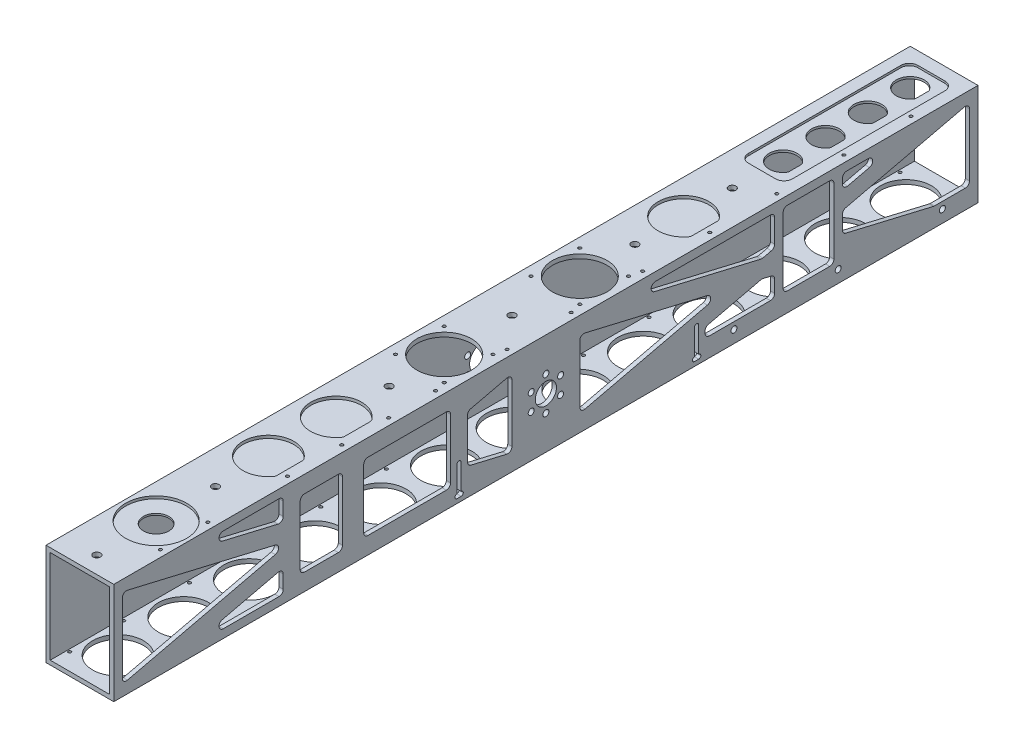
SolidWorks part; units mm, degrees
material "6061-T6 (SS)"
ref_plane "Front Plane" through (0, 0, 0) normal (0, 0, 1) x (1, 0, 0)
ref_plane "Top Plane" through (0, 0, 0) normal (0, 1, 0) x (1, 0, 0)
ref_plane "Right Plane" through (0, 0, 0) normal (1, 0, 0) x (0, 0, -1)
sketch "Sketch1" plane through (0, 0, 0) normal (0, 0, 1) x (1, 0, 0)
  line L0 (3.175, 3.175) -> (3.175, 73.025)
  line L1 (0, 0) -> (50.8, 0)
  line L2 (0, 0) -> (0, 76.2)
  line L3 (0, 76.2) -> (50.8, 76.2)
  line L4 (50.8, 0) -> (50.8, 76.2)
  line L5 (3.175, 73.025) -> (47.625, 73.025)
  line L6 (47.625, 3.175) -> (47.625, 73.025)
  line L7 (3.175, 3.175) -> (47.625, 3.175)
  dimension "D1" = 76.2
  dimension "D2" = 50.8
  dimension "D3" = 3.175
extrude "Boss-Extrude1" add sketch "Sketch1" along normal blind 647.7
sketch "Sketch2" plane through (50.8, 0, 0) normal (1, 0, 0) x (0, 0, -1)
  line L0 (-323.85, 76.2) -> (-323.85, 0) construction
  line L1 (-647.7, 76.2) -> (0, 76.2) construction
  line L2 (-647.7, 0) -> (0, 0) construction
  line L3 (-121.0655, 35.0094) -> (-10.2522, 8.9357)
  line L4 (-322.3956, 82.3812) -> (1.4544, 6.1812) construction
  line L5 (-649.1544, 6.1812) -> (-325.3044, 82.3812) construction
  line L6 (-646.2456, 82.3812) -> (-322.3956, 6.1812) construction
  line L7 (-649.1544, 70.0188) -> (-325.3044, -6.1812) construction
  line L8 (-647.7, 76.2) -> (-323.85, 0) construction
  line L9 (-647.7, 0) -> (-323.85, 76.2) construction
  line L10 (-323.85, 76.2) -> (0, 0) construction
  line L11 (-323.85, 0) -> (0, 76.2) construction
  line L12 (-6.35, 6.35) -> (-6.35, 69.85)
  line L13 (-6.35, 69.85) -> (-641.35, 69.85)
  line L14 (-641.35, 69.85) -> (-641.35, 6.35)
  line L15 (-641.35, 6.35) -> (-6.35, 6.35)
  line L16 (-6.35, 12.0263) -> (-6.35, 64.1737)
  line L17 (-646.2456, -6.1812) -> (-322.3956, 70.0188) construction
  line L18 (-641.35, 64.1737) -> (-641.35, 12.0263)
  line L19 (-641.35, 6.35) -> (-620.7125, 6.35)
  line L20 (-322.3956, -6.1812) -> (1.4544, 70.0188) construction
  line L21 (-325.3044, 6.1812) -> (-1.4544, 82.3812) construction
  line L22 (-161.1978, 44.7945) -> (-81.3408, 63.5844)
  line L23 (-161.1978, 31.4055) -> (-81.3408, 12.6156)
  line L24 (-241.782, 69.85) -> (-82.068, 69.85)
  line L25 (-647.7, 69.85) -> (0, 69.85)
  line L26 (-641.35, 69.85) -> (-620.7125, 69.85)
  line L27 (-241.782, 6.35) -> (-82.068, 6.35)
  line L28 (-566.3592, 63.5844) -> (-486.5022, 44.7945)
  line L29 (-637.4478, 67.2643) -> (-526.6345, 41.1906)
  line L30 (-637.4478, 8.9357) -> (-526.6345, 35.0094)
  line L31 (-566.3592, 12.6156) -> (-486.5022, 31.4055)
  line L32 (-242.5092, 63.5844) -> (-162.6522, 44.7945)
  line L33 (-325.3044, 70.0188) -> (-323.85, 69.6766)
  line L34 (-294.5478, 13.418) -> (-202.7845, 35.0094)
  line L35 (-242.5092, 12.6156) -> (-162.6522, 31.4055)
  line L36 (-349.25, 59.6914) -> (-349.25, 16.5086)
  line L37 (-298.45, 59.6914) -> (-298.45, 16.5086)
  line L38 (-294.5478, 62.782) -> (-202.7845, 41.1906)
  line L39 (-121.0655, 41.1906) -> (-10.2522, 67.2643)
  line L40 (-325.3044, 70.0188) -> (-1.4544, -6.1812) construction
  line L41 (-485.0478, 44.7945) -> (-405.1908, 63.5844)
  line L42 (-444.9155, 35.0094) -> (-353.1522, 13.418)
  line L43 (-444.9155, 41.1906) -> (-353.1522, 62.782)
  line L44 (-485.0478, 31.4055) -> (-405.1908, 12.6156)
  line L45 (-565.632, 69.85) -> (-405.918, 69.85)
  line L46 (-565.632, 6.35) -> (-405.918, 6.35)
  line L47 (-26.9875, 6.35) -> (-6.35, 6.35)
  line L48 (-26.9875, 69.85) -> (-6.35, 69.85)
  arc A0 (-405.918, 6.35) -> (-405.1908, 12.6156) centre (-405.918, 9.525) ccw
  arc A1 (-565.632, 6.35) -> (-566.3592, 12.6156) centre (-565.632, 9.525) cw
  arc A2 (-641.35, 64.1737) -> (-637.4478, 67.2643) centre (-638.175, 64.1737) cw
  arc A3 (-637.4478, 8.9357) -> (-641.35, 12.0263) centre (-638.175, 12.0263) cw
  arc A4 (-82.068, 6.35) -> (-81.3408, 12.6156) centre (-82.068, 9.525) ccw
  arc A5 (-241.782, 6.35) -> (-242.5092, 12.6156) centre (-241.782, 9.525) cw
  arc A6 (-6.35, 12.0263) -> (-10.2522, 8.9357) centre (-9.525, 12.0263) cw
  arc A7 (-6.35, 64.1737) -> (-10.2522, 67.2643) centre (-9.525, 64.1737) ccw
  arc A8 (-81.3408, 63.5844) -> (-82.068, 69.85) centre (-82.068, 66.675) ccw
  arc A9 (-242.5092, 63.5844) -> (-241.782, 69.85) centre (-241.782, 66.675) cw
  arc A10 (-121.0655, 41.1906) -> (-121.0655, 35.0094) centre (-120.3383, 38.1) ccw
  arc A11 (-161.1978, 31.4055) -> (-162.6522, 31.4055) centre (-161.925, 28.3149) ccw
  arc A12 (-161.1978, 44.7945) -> (-162.6522, 44.7945) centre (-161.925, 47.8851) cw
  arc A13 (-202.7845, 35.0094) -> (-202.7845, 41.1906) centre (-203.5117, 38.1) ccw
  arc A14 (-294.5478, 13.418) -> (-298.45, 16.5086) centre (-295.275, 16.5086) cw
  arc A15 (-294.5478, 62.782) -> (-298.45, 59.6914) centre (-295.275, 59.6914) ccw
  arc A16 (-353.1522, 62.782) -> (-349.25, 59.6914) centre (-352.425, 59.6914) cw
  arc A17 (-349.25, 16.5086) -> (-353.1522, 13.418) centre (-352.425, 16.5086) cw
  arc A18 (-485.0478, 31.4055) -> (-486.5022, 31.4055) centre (-485.775, 28.3149) ccw
  arc A19 (-526.6345, 35.0094) -> (-526.6345, 41.1906) centre (-527.3617, 38.1) ccw
  arc A20 (-444.9155, 35.0094) -> (-444.9155, 41.1906) centre (-444.1883, 38.1) cw
  arc A21 (-485.0478, 44.7945) -> (-486.5022, 44.7945) centre (-485.775, 47.8851) cw
  arc A22 (-405.1908, 63.5844) -> (-405.918, 69.85) centre (-405.918, 66.675) ccw
  arc A23 (-566.3592, 63.5844) -> (-565.632, 69.85) centre (-565.632, 66.675) cw
  point P69 (-592.988, 6.35)
  point P92 (-161.925, 44.6234)
  point P99 (-298.45, 63.7001)
  point P106 (-485.775, 31.5766)
  point P111 (-458.0505, 38.1)
  point P118 (-592.988, 69.85)
  dimension "D13" = 3.175
  dimension "D11" = 25.4
  dimension "D12" = 25.4
  dimension "D1" = 6.35
  dimension "D2" = 6.35
  dimension "D3" = 6.35
  dimension "D4" = 6.35
  dimension "D5" = 6.35
  dimension "D6" = 6.35
  dimension "D7" = 6.35
  dimension "D8" = 6.35
  dimension "D9" = 6.35
  dimension "D10" = 6.35
extrude "Cut-Extrude1" cut sketch "Sketch2" against normal through all contours A23 L28 A21 L41 A22 L45 | L30 A19 L29 A2 L18 A3 | L44 A18 L31 A1 L46 A0 | A20 L42 A17 L36 A16 L43 | L38 A15 L37 A14 L34 A13 | A12 L22 A8 L24 A9 L32 | L23 A11 L35 A5 L27 A4 | L39 A10 L3 A6 L16 A7
sketch "Sketch3" plane through (0, 76.2, 0) normal (0, 1, 0) x (1, 0, 0)
  line L0 (50.8, -647.7) -> (0, -647.7) construction
  line L1 (0, -647.7) -> (0, 0) construction
  circle A0 centre (25.4, -603.25) radius 19.05
  circle A1 centre (25.4, -552.45) radius 19.05
  circle A6 centre (25.4, -298.45) radius 19.05
  circle A7 centre (25.4, -247.65) radius 19.05
  circle A8 centre (25.4, -196.85) radius 19.05
  circle A10 centre (25.4, -95.25) radius 19.05
  circle A11 centre (25.4, -44.45) radius 19.05
  circle A12 centre (25.4, -501.65) radius 19.05
  circle A13 centre (25.4, -146.05) radius 19.05
  circle A14 centre (25.4, -349.25) radius 19.05
  circle A15 centre (25.4, -400.05) radius 19.05
  circle A16 centre (25.4, -450.85) radius 19.05
  dimension "D1" = 38.1
  dimension "D2" = 44.45
  dimension "D3" = 25.4
  dimension "D4" = 12
extrude "Cut-Extrude2" [suppressed] cut sketch "Sketch3" against normal through all
sketch "Sketch4" plane through (50.8, 0, 0) normal (1, 0, 0) x (0, 0, -1)
  line L0 (-647.7, 76.2) -> (0, 76.2) construction
  line L1 (-323.85, 76.2) -> (-323.85, 0) construction
  line L2 (-647.7, 0) -> (0, 0) construction
  circle A0 centre (-323.85, 38.1) radius 7.9375
  dimension "D2" = 15.875
  dimension "D1" = 38.1
extrude "Cut-Extrude3" cut sketch "Sketch4" against normal through all
sketch "Sketch5" plane through (0, 0, 0) normal (-1, 0, 0) x (0, 0, 1)
  circle A0 centre (323.85, 38.1) radius 9.525
  dimension "D1" = 19.05
extrude "Cut-Extrude4" cut sketch "Sketch5" against normal up to next
hole_wizard "#8 Clearance Hole1" positions "Sketch7" profile "Sketch6" hole size "#8" standard "Ansi Inch" end condition through all
sketch "Sketch7" plane through (0, 0, 0) normal (-1, 0, 0) x (0, 0, 1)
  line L0 (647.7, 76.2) -> (0, 76.2) construction
  line L1 (323.85, 76.2) -> (323.85, 0) construction
  line L2 (647.7, 0) -> (0, 0) construction
  circle A0 centre (323.85, 38.1) radius 9.525 construction
  point P0 (323.85, 50.8)
  point P15 (323.85, 76.2)
  dimension "D1" = 12.7
sketch "Sketch6" plane through (0, 50.8, 323.85) normal (0, 1, 0) x (0, 0, 1)
  line L0 (0, 0) -> (0, 50.8)
  line L1 (0, 50.8) -> (2.2479, 50.8)
  line L2 (2.2479, 50.8) -> (2.2479, 0)
  line L5 (2.2479, 0) -> (0, 0)
  line L11 (0, -6.35) -> (0, 107.95) construction
  dimension "Thru Hole Dia." = 4.4958
  dimension "Thru Hole Depth" = 50.8
pattern_circular "CirPattern1" count 6 over 360 about axis through (0, 38.1, 323.85) along (1, 0, 0) of "#8 Clearance Hole1"
hole_wizard "1/4-28 Tapped Hole1" positions "Sketch9" profile "Sketch8" tap size "1/4-28" standard "Ansi Inch"
sketch "Sketch9" plane through (0, 76.2, 0) normal (0, 1, 0) x (-1, 0, 0)
  line L0 (-25.4, 647.7) -> (-25.4, 0) construction
  line L1 (-50.8, 647.7) -> (0, 647.7) construction
  line L2 (-50.8, 0) -> (0, 0) construction
  point P0 (-25.4, 498.475)
  point P1 (-25.4, 323.85)
  point P5 (-25.4, 149.225)
  point P20 (-25.4, 323.85)
  dimension "D1" = 149.225
  dimension "D2" = 149.225
sketch "Sketch8" plane through (25.4, 76.2, 498.475) normal (1, 0, 0) x (0, 0, 1)
  line L0 (0, 0) -> (0, 76.2)
  line L1 (0, 76.2) -> (2.7051, 76.2)
  line L2 (2.7051, 76.2) -> (2.7051, 0)
  line L5 (2.7051, 0) -> (0, 0)
  line L11 (0, -6.35) -> (0, 107.95) construction
  dimension "Thru Tap Drill Dia." = 5.4102
  dimension "Thru Tap Drill Depth" = 76.2
cosmetic thread "Hole Thread1" [suppressed]
cosmetic thread "Hole Thread2" [suppressed]
cosmetic thread "Hole Thread3" [suppressed]
sketch "Sketch10" plane through (50.8, 0, 0) normal (1, 0, 0) x (0, 0, -1)
  line L0 (-647.7, 0) -> (0, 0) construction
  line L1 (-520.7, 0) -> (-463.55, 0)
  line L2 (-520.7, 0) -> (-520.7, 76.2)
  line L3 (-520.7, 76.2) -> (-463.55, 76.2)
  line L4 (-463.55, 0) -> (-463.55, 76.2)
  line L5 (-647.7, 76.2) -> (0, 76.2) construction
  line L6 (-647.7, 0) -> (-647.7, 76.2) construction
  dimension "D1" = 127
  dimension "D2" = 57.15
extrude "Boss-Extrude2" add sketch "Sketch10" against normal blind 3.175
sketch "Sketch12" plane through (0, 76.2, 0) normal (0, 1, 0) x (1, 0, 0)
  line L0 (0, -647.7) -> (0, 0) construction
  line L1 (7.1374, -291.3126) -> (43.6626, -291.3126) construction
  line L2 (7.1374, -291.3126) -> (7.1374, -254.7874) construction
  line L3 (7.1374, -254.7874) -> (43.6626, -254.7874) construction
  line L4 (43.6626, -291.3126) -> (43.6626, -254.7874) construction
  line L5 (7.1374, -291.3126) -> (43.6626, -254.7874) construction
  line L6 (7.1374, -254.7874) -> (43.6626, -291.3126) construction
  line L9 (50.8, 0) -> (0, 0) construction
  line L10 (7.1374, -392.9126) -> (43.6626, -392.9126) construction
  line L11 (7.1374, -392.9126) -> (7.1374, -356.3874) construction
  line L12 (7.1374, -356.3874) -> (43.6626, -356.3874) construction
  line L13 (43.6626, -392.9126) -> (43.6626, -356.3874) construction
  line L14 (7.1374, -392.9126) -> (43.6626, -356.3874) construction
  line L15 (7.1374, -356.3874) -> (43.6626, -392.9126) construction
  line L16 (7.1374, -323.85) -> (43.6626, -323.85) construction
  line L17 (25.4, -293.497) -> (25.4, -354.203) construction
  line L19 (25.4, 25.4) -> (25.4, -622.3) construction
  line L20 (25.4, -76.2) -> (25.4, -723.9) construction
  circle A0 centre (25.4, -273.05) radius 20.447
  circle A1 centre (25.4, -374.65) radius 20.447
  point P0 (25.4, -273.05)
  point P5 (25.4, -323.85)
  point P15 (25.4, -374.65)
  dimension "D3" = 40.894
  dimension "D5" = 25.4
  dimension "D7" = 323.85
  dimension "D1" = 36.5252
  dimension "D2" = 36.5252
  dimension "D6" = 101.6
  dimension "D4" = 2
extrude "Cut-Extrude5" cut sketch "Sketch12" against normal up to next
hole_wizard "#4-40 Tapped Hole1" positions "Sketch14" profile "Sketch15" tap size "#4-40" standard "Ansi Inch" end condition up to next
sketch "Sketch14" plane through (0, 76.2, 0) normal (0, 1, 0) x (-1, 0, 0)
  point P0 (-7.1374, 254.7874)
  point P1 (-43.6626, 254.7874)
  point P4 (-43.6626, 291.3126)
  point P7 (-7.1374, 291.3126)
  point P10 (-7.1374, 356.3874)
  point P13 (-43.6626, 356.3874)
  point P16 (-7.1374, 392.9126)
  point P19 (-43.6626, 392.9126)
sketch "Sketch15" plane through (7.1374, 76.2, 254.7874) normal (1, 0, 0) x (0, 0, 1)
  line L0 (0, 0) -> (0, 3.175)
  line L1 (0, 3.175) -> (1.1303, 3.175)
  line L2 (1.1303, 3.175) -> (1.1303, 0)
  line L5 (1.1303, 0) -> (0, 0)
  line L11 (0, -6.35) -> (0, 107.95) construction
  dimension "Thru Tap Drill Dia." = 2.2606
  dimension "Thru Tap Drill Depth" = 3.175
cosmetic thread "Hole Thread4"
cosmetic thread "Hole Thread5"
cosmetic thread "Hole Thread6"
cosmetic thread "Hole Thread7"
cosmetic thread "Hole Thread8"
cosmetic thread "Hole Thread9"
cosmetic thread "Hole Thread10"
cosmetic thread "Hole Thread11"
sketch "Sketch17" plane through (50.8, 0, 0) normal (1, 0, 0) x (0, 0, -1)
  line L0 (-492.125, 76.2) -> (-492.125, 0) construction
  line L1 (-647.7, 76.2) -> (0, 76.2) construction
  line L2 (-647.7, 0) -> (0, 0) construction
  line L3 (-647.7, 0) -> (-647.7, 76.2) construction
  line L6 (-508, 12.7) -> (-476.25, 12.7)
  line L7 (-508, 12.7) -> (-508, 63.5)
  line L8 (-508, 63.5) -> (-476.25, 63.5)
  line L9 (-476.25, 12.7) -> (-476.25, 63.5)
  line L10 (-508, 12.7) -> (-476.25, 63.5) construction
  line L11 (-508, 63.5) -> (-476.25, 12.7) construction
  point P8 (-492.125, 38.1)
  dimension "D1" = 139.7
  dimension "D2" = 50.8
  dimension "D3" = 31.75
extrude "Cut-Extrude6" cut sketch "Sketch17" against normal up to next
sketch "Sketch18" plane through (0, 76.2, 0) normal (0, 1, 0) x (1, 0, 0)
  line L0 (25.4, 0) -> (25.4, -647.7) construction
  line L1 (50.8, 0) -> (0, 0) construction
  line L2 (50.8, -647.7) -> (0, -647.7) construction
  line L3 (34.4043, -115.4433) -> (34.4043, -125.8567)
  arc A0 (34.4043, -115.4433) -> (34.4043, -125.8567) centre (25.4, -120.65) ccw
  dimension "D1" = 20.8026
  dimension "D2" = 120.65
  dimension "D3" = 9.0043
extrude "Cut-Extrude7" cut sketch "Sketch18" against normal up to next
pattern_linear "LPattern1" count 4 spacing 31.75 along (0, 0, -1) of "Cut-Extrude7"
sketch "Sketch19" plane through (0, 76.2, 0) normal (0, 1, 0) x (1, 0, 0)
  line L0 (50.8, -647.7) -> (50.8, 0) construction
  line L1 (15.24, -9.525) -> (35.56, -9.525)
  line L2 (8.89, -15.875) -> (8.89, -130.175)
  line L3 (15.24, -136.525) -> (35.56, -136.525)
  line L4 (41.91, -15.875) -> (41.91, -130.175)
  line L5 (0, -647.7) -> (0, 0) construction
  arc A0 (35.56, -136.525) -> (41.91, -130.175) centre (35.56, -130.175) ccw
  arc A1 (8.89, -130.175) -> (15.24, -136.525) centre (15.24, -130.175) ccw
  arc A2 (35.56, -9.525) -> (41.91, -15.875) centre (35.56, -15.875) cw
  arc A3 (15.24, -9.525) -> (8.89, -15.875) centre (15.24, -15.875) ccw
  arc A4 (34.4043, -20.1933) -> (34.4043, -30.6067) centre (25.4, -25.4) ccw construction
  point P12 (41.91, -136.525)
  point P17 (41.91, -9.525)
  dimension "D5" = 6.35
  dimension "D3" = 15.875
  dimension "D1" = 8.89
  dimension "D2" = 8.89
  dimension "D4" = 127
extrude "Cut-Extrude8" cut sketch "Sketch19" against normal blind 1.5875
ref_plane "Plane1" through (0, 38.1, 0) normal (0, 1, 0) x (-1, 0, 0)
sketch "Sketch20" [suppressed] plane through (0, 0, 0) normal (0, -1, 0) x (1, 0, 0)
  line L0 (25.4, 647.7) -> (25.4, 498.475) construction
  line L1 (0, 647.7) -> (50.8, 647.7) construction
  line L3 (13.0937, 603.6437) -> (37.7063, 603.6437) construction
  line L4 (13.0937, 603.6437) -> (13.0937, 628.2563) construction
  line L5 (13.0937, 628.2563) -> (37.7063, 628.2563) construction
  line L6 (37.7063, 603.6437) -> (37.7063, 628.2563) construction
  line L7 (13.0937, 603.6437) -> (37.7063, 628.2563) construction
  line L8 (13.0937, 628.2563) -> (37.7063, 603.6437) construction
  circle A0 centre (25.4, 615.95) radius 12.4333
  point P5 (25.4, 615.95)
  dimension "D3" = 24.8666
  dimension "D1" = 24.6126
  dimension "D2" = 24.6126
  dimension "D4" = 31.75
hole_wizard "1/4-28 Tapped Hole2" positions "Sketch22" profile "Sketch21" tap size "1/4-28" standard "Ansi Inch" end condition up to next
sketch "Sketch22" plane through (0, 76.2, 0) normal (0, 1, 0) x (-1, 0, 0)
  line L0 (-25.4, 0) -> (-25.4, 647.7) construction
  line L1 (-50.8, 0) -> (0, 0) construction
  line L2 (-50.8, 647.7) -> (0, 647.7) construction
  point P0 (-25.4, 158.75)
  point P10 (-25.4, 231.775)
  point P12 (-25.4, 323.85)
  point P14 (-25.4, 415.925)
  point P16 (-25.4, 546.1)
  point P18 (-25.4, 635)
  dimension "D1" = 158.75
  dimension "D2" = 73.025
  dimension "D3" = 92.075
  dimension "D4" = 130.175
  dimension "D5" = 88.9
cosmetic thread "Hole Thread12"
cosmetic thread "Hole Thread13"
cosmetic thread "Hole Thread14"
cosmetic thread "Hole Thread15"
cosmetic thread "Hole Thread16"
cosmetic thread "Hole Thread17"
sketch "Sketch21" plane through (25.4, 76.2, 158.75) normal (1, 0, 0) x (0, 0, 1)
  line L0 (0, 0) -> (0, 3.175)
  line L1 (0, 3.175) -> (2.7051, 3.175)
  line L2 (2.7051, 3.175) -> (2.7051, 0)
  line L5 (2.7051, 0) -> (0, 0)
  line L11 (0, -6.35) -> (0, 107.95) construction
  dimension "Thru Tap Drill Dia." = 5.4102
  dimension "Thru Tap Drill Depth" = 3.175
sketch "Sketch23" plane through (0, 76.2, 0) normal (0, 1, 0) x (1, 0, 0)
  line L0 (0, -647.7) -> (0, 0) construction
  circle A0 centre (25.4, -195.2625) radius 19.05
  circle A1 centre (25.4, -231.775) radius 2.7051 construction
  circle A2 centre (25.4, -546.1) radius 2.7051 construction
  circle A3 centre (25.4, -455.6125) radius 19.05
  circle A4 centre (25.4, -506.4125) radius 19.05
  circle A5 centre (25.4, -415.925) radius 2.7051 construction
  circle A7 centre (25.4, -590.55) radius 19.05
  dimension "D1" = 38.1
  dimension "D3" = 36.5125
  dimension "D6" = 44.45
  dimension "D2" = 25.4
  dimension "D4" = 50.8
  dimension "D5" = 39.6875
extrude "Cut-Extrude9" cut sketch "Sketch23" against normal up to next
sketch "Sketch24" plane through (0, 0, 0) normal (0, -1, 0) x (1, 0, 0)
  line L0 (0, 647.7) -> (0, 0) construction
  line L1 (0, 647.7) -> (50.8, 647.7) construction
  circle A0 centre (25.4, 619.125) radius 19.05
  circle A1 centre (25.4, 569.9125) radius 19.05
  circle A2 centre (25.4, 520.7) radius 19.05
  circle A3 centre (25.4, 471.4875) radius 19.05
  circle A4 centre (25.4, 422.275) radius 19.05
  circle A5 centre (25.4, 373.0625) radius 19.05
  circle A6 centre (25.4, 323.85) radius 19.05
  circle A7 centre (25.4, 274.6375) radius 19.05
  circle A8 centre (25.4, 225.425) radius 19.05
  circle A9 centre (25.4, 176.2125) radius 19.05
  circle A10 centre (25.4, 127) radius 19.05
  circle A11 centre (25.4, 77.7875) radius 19.05
  circle A12 centre (25.4, 28.575) radius 19.05
  dimension "D1" = 38.1
  dimension "D2" = 25.4
  dimension "D3" = 28.575
  dimension "D5" = 49.2125
  dimension "D4" = 13
extrude "Cut-Extrude10" cut sketch "Sketch24" against normal up to next
sketch "Sketch25" plane through (50.8, 0, 0) normal (1, 0, 0) x (0, 0, -1)
  line L0 (-388.9375, 76.2) -> (-388.9375, 0) construction
  line L1 (-647.7, 76.2) -> (0, 76.2) construction
  line L2 (-647.7, 0) -> (0, 0) construction
  line L3 (-395.2875, 52.8678) -> (-395.2875, 23.3322)
  line L4 (-382.5875, 55.856) -> (-382.5875, 20.344)
  line L5 (-647.7, 0) -> (-647.7, 76.2) construction
  line L6 (-395.2875, 52.8678) -> (-382.5875, 55.856)
  line L7 (-444.9155, 41.1906) -> (-353.1522, 62.782) construction
  line L8 (-395.2875, 23.3322) -> (-382.5875, 20.344)
  line L9 (-444.9155, 35.0094) -> (-353.1522, 13.418) construction
  line L10 (-395.2875, 76.2) -> (-395.2875, 0) construction
  line L11 (-382.5875, 76.2) -> (-382.5875, 0) construction
  dimension "D3" = 258.7625
  dimension "D1" = 6.35
  dimension "D2" = 6.35
extrude "Boss-Extrude3" add sketch "Sketch25" against normal up to surface (3.175 mm away) up to face at (47.625, 38.1, 492.125)
sketch "Sketch28" plane through (50.8, 0, 0) normal (1, 0, 0) x (0, 0, -1)
  line L0 (0, 0) -> (0, 76.2) construction
  line L3 (-242.5092, 12.6156) -> (-162.6522, 31.4055) construction
  line L4 (-241.782, 6.35) -> (-82.068, 6.35) construction
  line L9 (-242.5092, 12.6156) -> (-204.5335, 21.5511)
  line L10 (-241.782, 6.35) -> (-204.5335, 6.35)
  line L11 (-204.5335, 21.5511) -> (-204.5335, 6.35)
  arc A1 (-242.5092, 12.6156) -> (-241.782, 6.35) centre (-241.782, 9.525) ccw construction
  arc A3 (-242.5092, 12.6156) -> (-241.782, 6.35) centre (-241.782, 9.525) ccw
  dimension "D1" = 204.5335
extrude "Boss-Extrude6" add sketch "Sketch28" against normal up to surface (3.175 mm away) up to face at (47.625, 38.1, 420.7134)
sketch "Sketch30" [suppressed] plane through (50.8, 0, 0) normal (1, 0, 0) x (0, 0, -1)
  line L0 (-384.175, 27.94) -> (-384.175, 8.89) construction
  line L1 (-387.35, 8.89) -> (-387.35, 27.94) construction
  line L2 (-384.175, 5.715) -> (-387.35, 5.715) construction
  line L3 (-215.646, 6.35) -> (-215.646, 25.4) construction
  line L4 (-212.471, 25.4) -> (-212.471, 6.35) construction
  line L5 (-212.471, 3.175) -> (-215.646, 3.175) construction
  line L6 (-384.175, 27.94) -> (-384.175, 8.89)
  line L7 (-387.35, 8.89) -> (-387.35, 27.94)
  line L8 (-384.175, 5.715) -> (-387.35, 5.715)
  line L9 (-215.646, 6.35) -> (-215.646, 25.4)
  line L10 (-212.471, 25.4) -> (-212.471, 6.35)
  line L11 (-212.471, 3.175) -> (-215.646, 3.175)
  arc A0 (-384.175, 27.94) -> (-387.35, 27.94) centre (-385.7625, 27.94) ccw construction
  arc A1 (-387.35, 8.89) -> (-387.35, 5.715) centre (-387.35, 7.3025) ccw construction
  arc A2 (-384.175, 5.715) -> (-384.175, 8.89) centre (-384.175, 7.3025) ccw construction
  arc A3 (-215.646, 6.35) -> (-215.646, 3.175) centre (-215.646, 4.7625) ccw construction
  arc A4 (-212.471, 25.4) -> (-215.646, 25.4) centre (-214.0585, 25.4) ccw construction
  arc A5 (-212.471, 3.175) -> (-212.471, 6.35) centre (-212.471, 4.7625) ccw construction
  arc A6 (-384.175, 27.94) -> (-387.35, 27.94) centre (-385.7625, 27.94) ccw
  arc A7 (-387.35, 8.89) -> (-387.35, 5.715) centre (-387.35, 7.3025) ccw
  arc A8 (-384.175, 5.715) -> (-384.175, 8.89) centre (-384.175, 7.3025) ccw
  arc A9 (-215.646, 6.35) -> (-215.646, 3.175) centre (-215.646, 4.7625) ccw
  arc A10 (-212.471, 25.4) -> (-215.646, 25.4) centre (-214.0585, 25.4) ccw
  arc A11 (-212.471, 3.175) -> (-212.471, 6.35) centre (-212.471, 4.7625) ccw
sketch "Sketch31" plane through (50.8, 0, 0) normal (1, 0, 0) x (0, 0, -1)
  line L0 (-390.525, 26.9875) -> (-390.525, 6.35)
  line L1 (-390.525, 6.35) -> (-392.1125, 6.35)
  line L2 (-392.1125, 6.35) -> (-392.1125, 3.175)
  line L3 (-392.1125, 3.175) -> (-385.7625, 3.175)
  line L4 (-385.7625, 3.175) -> (-385.7625, 6.35)
  line L5 (-385.7625, 6.35) -> (-387.35, 6.35)
  line L6 (-387.35, 6.35) -> (-387.35, 26.9875)
  line L7 (-387.35, 26.9875) -> (-390.525, 26.9875)
  line L8 (-647.7, 0) -> (0, 0) construction
  line L9 (-382.5875, 20.344) -> (-382.5875, 55.856) construction
  line L10 (-388.9375, 26.9875) -> (-388.9375, 3.175) construction
  dimension "D1" = 3.175
  dimension "D2" = 3.175
  dimension "D3" = 3.175
  dimension "D4" = 4.7625
  dimension "D5" = 23.8125
  dimension "D6" = 3.175
  dimension "D7" = 3.175
extrude "Cut-Extrude13" cut sketch "Sketch31" against normal up to next
fillet "Fillet2" radius 1.5875 6 edges at (49.2125, 26.9875, 387.35) (49.2125, 26.9875, 390.525) (49.2125, 6.35, 385.7625) (49.2125, 3.175, 385.7625) (49.2125, 3.175, 392.1125) (49.2125, 6.35, 392.1125)
pattern_linear "LPattern2" count 2 spacing 178.054 along (0, 0, -1) of "Cut-Extrude13", "Fillet2"
fillet "Fillet3" radius 3.175 18 edges at (49.2125, 6.35, 204.5335) (49.2125, 21.5511, 204.5335) (49.2125, 55.856, 382.5875) (49.2125, 20.344, 382.5875) (49.2125, 23.3322, 395.2875) (49.2125, 52.8678, 395.2875) (49.2125, 69.85, 463.55) (49.2125, 49.8528, 463.55) (49.2125, 26.3472, 463.55) (49.2125, 6.35, 463.55) (49.2125, 12.7, 476.25) (49.2125, 12.7, 508) (49.2125, 63.5, 476.25) (49.2125, 63.5, 508) (49.2125, 69.85, 520.7) (49.2125, 52.8411, 520.7) (49.2125, 6.35, 520.7) (49.2125, 23.3589, 520.7)
sketch "Sketch32" plane through (50.8, 0, 0) normal (1, 0, 0) x (0, 0, -1)
  line L0 (-204.5335, 9.525) -> (-204.5335, 19.0364) construction
  line L1 (0, 0) -> (-204.5335, 0)
  line L2 (0, 0) -> (0, 14.2875)
  line L3 (0, 14.2875) -> (-204.5335, 14.2875)
  line L4 (-204.5335, 0) -> (-204.5335, 14.2875)
  dimension "D1" = 14.2875
extrude "Boss-Extrude7" add sketch "Sketch32" against normal up to surface (3.175 mm away) up to face at (47.625, 16.6564, 304.2631)
fillet "Fillet4" radius 3.175 4 edges at (49.2125, 14.2875, 204.5335) (49.2125, 14.2875, 88.4464) (49.2125, 14.2875, 32.9974) (49.2125, 14.2875, 6.35)
hole_wizard "#8 Clearance Hole2" positions "Sketch36" profile "Sketch37" hole size "#8" standard "Ansi Inch" end condition up to next
sketch "Sketch36" plane through (50.8, 0, 0) normal (1, 0, 0) x (0, 0, -1)
  line L0 (0, 0) -> (0, 76.2) construction
  line L1 (-647.7, 0) -> (0, 0) construction
  point P0 (-26.67, 9.2075)
  point P1 (-104.775, 9.2075)
  point P3 (-182.88, 9.2075)
  dimension "D1" = 26.67
  dimension "D2" = 78.105
  dimension "D3" = 78.105
  dimension "D4" = 9.2075
sketch "Sketch37" plane through (50.8, 9.2075, 26.67) normal (0, 1, 0) x (0, 0, -1)
  line L0 (0, 0) -> (0, 3.175)
  line L1 (0, 3.175) -> (2.2479, 3.175)
  line L2 (2.2479, 3.175) -> (2.2479, 0)
  line L5 (2.2479, 0) -> (0, 0)
  line L11 (0, -6.35) -> (0, 107.95) construction
  dimension "Thru Hole Dia." = 4.4958
  dimension "Thru Hole Depth" = 3.175
sketch "Sketch38" plane through (0, 0, 0) normal (-1, 0, 0) x (0, 0, 1)
  line L0 (115.8024, 14.2875) -> (201.3585, 14.2875) construction
  line L1 (0, 0) -> (254, 0)
  line L2 (0, 0) -> (0, 14.2875)
  line L3 (0, 14.2875) -> (254, 14.2875)
  line L4 (254, 0) -> (254, 14.2875)
  dimension "D1" = 254
extrude "Boss-Extrude8" add sketch "Sketch38" against normal up to surface (3.175 mm away) up to face at (3.175, 44.45, 332.6006)
fillet "Fillet5" radius 3.175 4 edges at (1.5875, 14.2875, 6.35) (1.5875, 14.2875, 32.9974) (1.5875, 14.2875, 88.4464) (1.5875, 14.2875, 235.4036)
hole_wizard "#8 Clearance Hole3" positions "Sketch40" profile "Sketch39" hole size "#8" standard "Ansi Inch"
sketch "Sketch40" plane through (3.175, 0, 0) normal (1, 0, 0) x (0, 0, -1)
  point P1 (-104.775, 9.2075)
  point P4 (-26.67, 9.2075)
  point P7 (-182.88, 9.2075)
sketch "Sketch39" plane through (3.175, 9.2075, 104.775) normal (0, 1, 0) x (0, 0, -1)
  line L0 (0, 0) -> (0, 4.6527)
  line L1 (0, 4.6527) -> (2.2479, 3.302)
  line L2 (2.2479, 3.302) -> (2.2479, 0)
  line L5 (2.2479, 0) -> (0, 0)
  line L10 (0, 4.6527) -> (-2.2479, 3.302) construction
  line L11 (0, -6.35) -> (0, 107.95) construction
  dimension "Hole Dia." = 4.4958
  dimension "Hole Depth" = 3.302
  dimension "Drill Angle" = 118
sketch "Sketch41" plane through (50.8, 0, 0) normal (1, 0, 0) x (0, 0, -1)
  line L0 (-647.7, 76.2) -> (0, 76.2) construction
  line L1 (-463.55, 76.2) -> (-395.2875, 76.2)
  line L2 (-463.55, 76.2) -> (-463.55, 0)
  line L3 (-463.55, 0) -> (-395.2875, 0)
  line L4 (-395.2875, 76.2) -> (-395.2875, 0)
  line L5 (-463.55, 53.8616) -> (-463.55, 66.675) construction
  line L6 (-647.7, 0) -> (0, 0) construction
  line L7 (-395.2875, 48.859) -> (-395.2875, 27.341) construction
extrude "Boss-Extrude9" add sketch "Sketch41" against normal up to surface (3.175 mm away) up to face at (47.625, 9.2075, 28.9179)
sketch "Sketch42" plane through (50.8, 0, 0) normal (1, 0, 0) x (0, 0, -1)
  line L0 (-479.425, 63.5) -> (-504.825, 63.5) construction
  line L1 (-457.2, 63.5) -> (-398.4625, 63.5)
  line L2 (-460.375, 60.325) -> (-460.375, 15.875)
  line L3 (-457.2, 12.7) -> (-398.4625, 12.7)
  line L4 (-395.2875, 60.325) -> (-395.2875, 15.875)
  line L5 (-504.825, 12.7) -> (-479.425, 12.7) construction
  line L6 (-476.25, 15.875) -> (-476.25, 60.325) construction
  line L7 (-382.5875, 22.8586) -> (-382.5875, 53.3414) construction
  arc A0 (-398.4625, 12.7) -> (-395.2875, 15.875) centre (-398.4625, 15.875) ccw
  arc A1 (-460.375, 15.875) -> (-457.2, 12.7) centre (-457.2, 15.875) ccw
  arc A2 (-398.4625, 63.5) -> (-395.2875, 60.325) centre (-398.4625, 60.325) cw
  arc A3 (-457.2, 63.5) -> (-460.375, 60.325) centre (-457.2, 60.325) ccw
  dimension "D3" = 3.175
  dimension "D1" = 15.875
  dimension "D2" = 12.7
extrude "Cut-Extrude14" cut sketch "Sketch42" against normal up to next
sketch "Sketch43" plane through (50.8, 0, 0) normal (1, 0, 0) x (0, 0, -1)
  line L0 (-647.7, 76.2) -> (0, 76.2) construction
  line L1 (-152.4, 76.2) -> (-101.6, 76.2)
  line L2 (-152.4, 76.2) -> (-152.4, 14.2875)
  line L3 (-152.4, 14.2875) -> (-101.6, 14.2875)
  line L4 (-101.6, 76.2) -> (-101.6, 14.2875)
  line L5 (-115.8024, 14.2875) -> (-201.3585, 14.2875) construction
  line L6 (0, 0) -> (0, 76.2) construction
  dimension "D1" = 101.6
  dimension "D2" = 50.8
extrude "Boss-Extrude10" add sketch "Sketch43" against normal up to surface (3.175 mm away) up to face at (47.625, 38.1, 427.8312)
fillet "Fillet6" radius 3.175 8 edges at (49.2125, 69.85, 101.6) (49.2125, 58.8175, 101.6) (49.2125, 45.7707, 101.6) (49.2125, 30.4293, 101.6) (49.2125, 14.2875, 152.4) (49.2125, 29.3354, 152.4) (49.2125, 69.85, 152.4) (49.2125, 46.8646, 152.4)
sketch "Sketch44" plane through (50.8, 0, 0) normal (1, 0, 0) x (0, 0, -1)
  line L0 (-152.4, 66.675) -> (-152.4, 49.3792) construction
  line L1 (-142.875, 69.85) -> (-111.125, 69.85)
  line L2 (-146.05, 66.675) -> (-146.05, 17.4625)
  line L3 (-142.875, 14.2875) -> (-111.125, 14.2875)
  line L4 (-107.95, 66.675) -> (-107.95, 17.4625)
  line L5 (-647.7, 76.2) -> (0, 76.2) construction
  line L6 (-155.575, 14.2875) -> (-201.3585, 14.2875) construction
  line L7 (-101.6, 32.9439) -> (-101.6, 43.2561) construction
  arc A0 (-111.125, 69.85) -> (-107.95, 66.675) centre (-111.125, 66.675) cw
  arc A1 (-111.125, 14.2875) -> (-107.95, 17.4625) centre (-111.125, 17.4625) ccw
  arc A2 (-146.05, 17.4625) -> (-142.875, 14.2875) centre (-142.875, 17.4625) ccw
  arc A3 (-142.875, 69.85) -> (-146.05, 66.675) centre (-142.875, 66.675) ccw
  dimension "D4" = 3.175
  dimension "D1" = 6.35
  dimension "D2" = 6.35
  dimension "D3" = 6.35
extrude "Cut-Extrude15" cut sketch "Sketch44" against normal up to next
sketch "Sketch45" plane through (0, 76.2, 0) normal (0, 1, 0) x (1, 0, 0)
  circle A0 centre (25.4, -590.55) radius 19.05
  circle A1 centre (25.4, -590.55) radius 19.05 construction
extrude "Boss-Extrude12" add sketch "Sketch45" against normal up to surface (3.175 mm away) up to face at (25.4, 73.025, 571.5)
sketch "Sketch46" plane through (0, 76.2, 0) normal (0, 1, 0) x (1, 0, 0)
  line L0 (50.8, -647.7) -> (0, -647.7) construction
  line L1 (0, -647.7) -> (0, 0) construction
  circle A0 centre (25.4, -590.55) radius 22.86
  dimension "D1" = 45.72
  dimension "D2" = 57.15
  dimension "D3" = 25.4
extrude "Cut-Extrude16" cut sketch "Sketch46" against normal blind 1.905
sketch "Sketch47" plane through (0, 74.295, 0) normal (0, 1, 0) x (1, 0, 0)
  circle A0 centre (25.4, -590.55) radius 9.525
  dimension "D1" = 19.05
extrude "Cut-Extrude17" cut sketch "Sketch47" against normal up to next
sketch "Sketch48" plane through (3.175, 0, 0) normal (1, 0, 0) x (0, 0, -1)
  line L0 (-444.9155, 41.1906) -> (-353.1522, 62.782) construction
  line L1 (-444.9155, 41.1906) -> (-353.1522, 62.782)
  line L3 (-637.4478, 8.9357) -> (-526.6345, 35.0094)
  line L4 (-641.35, 64.1737) -> (-641.35, 12.0263)
  line L5 (-526.6345, 41.1906) -> (-637.4478, 67.2643)
  line L6 (-637.4478, 8.9357) -> (-526.6345, 35.0094)
  line L7 (-641.35, 64.1737) -> (-641.35, 12.0263)
  line L8 (-526.6345, 41.1906) -> (-637.4478, 67.2643)
  line L9 (-405.1908, 12.6156) -> (-485.0478, 31.4055)
  line L10 (-565.632, 6.35) -> (-405.918, 6.35)
  line L11 (-486.5022, 31.4055) -> (-566.3592, 12.6156)
  line L12 (-405.1908, 12.6156) -> (-485.0478, 31.4055)
  line L13 (-565.632, 6.35) -> (-405.918, 6.35)
  line L14 (-486.5022, 31.4055) -> (-566.3592, 12.6156)
  line L15 (-566.3592, 63.5844) -> (-486.5022, 44.7945)
  line L16 (-405.918, 69.85) -> (-565.632, 69.85)
  line L17 (-485.0478, 44.7945) -> (-405.1908, 63.5844)
  line L18 (-566.3592, 63.5844) -> (-486.5022, 44.7945)
  line L19 (-405.918, 69.85) -> (-565.632, 69.85)
  line L20 (-485.0478, 44.7945) -> (-405.1908, 63.5844)
  line L21 (-444.9155, 35.0094) -> (-353.1522, 13.418)
  line L22 (-353.1522, 62.782) -> (-444.9155, 41.1906)
  line L23 (-349.25, 16.5086) -> (-349.25, 59.6914)
  line L24 (-444.9155, 35.0094) -> (-353.1522, 13.418)
  line L25 (-353.1522, 62.782) -> (-444.9155, 41.1906)
  line L26 (-349.25, 16.5086) -> (-349.25, 59.6914)
  line L27 (-202.7845, 41.1906) -> (-294.5478, 62.782)
  line L28 (-294.5478, 13.418) -> (-202.7845, 35.0094)
  line L29 (-298.45, 59.6914) -> (-298.45, 16.5086)
  line L30 (-202.7845, 41.1906) -> (-294.5478, 62.782)
  line L31 (-294.5478, 13.418) -> (-202.7845, 35.0094)
  line L32 (-298.45, 59.6914) -> (-298.45, 16.5086)
  line L33 (-161.1978, 44.7945) -> (-81.3408, 63.5844)
  line L34 (-242.5092, 63.5844) -> (-162.6522, 44.7945)
  line L35 (-82.068, 69.85) -> (-241.782, 69.85)
  line L36 (-161.1978, 44.7945) -> (-81.3408, 63.5844)
  line L37 (-242.5092, 63.5844) -> (-162.6522, 44.7945)
  line L38 (-82.068, 69.85) -> (-241.782, 69.85)
  line L39 (-115.0752, 20.5531) -> (-161.1978, 31.4055)
  line L40 (-208.0476, 14.2875) -> (-115.8024, 14.2875)
  line L41 (-162.6522, 31.4055) -> (-208.7748, 20.5531)
  line L42 (-115.0752, 20.5531) -> (-161.1978, 31.4055)
  line L43 (-208.0476, 14.2875) -> (-115.8024, 14.2875)
  line L44 (-162.6522, 31.4055) -> (-208.7748, 20.5531)
  line L46 (-6.35, 17.4625) -> (-6.35, 64.1737)
  line L47 (-32.6289, 14.2875) -> (-9.525, 14.2875)
  line L48 (-121.0655, 35.0094) -> (-33.3561, 14.3719)
  line L49 (-10.2522, 67.2643) -> (-121.0655, 41.1906)
  line L50 (-6.35, 17.4625) -> (-6.35, 64.1737)
  line L51 (-32.6289, 14.2875) -> (-9.525, 14.2875)
  line L52 (-121.0655, 35.0094) -> (-33.3561, 14.3719)
  line L53 (-10.2522, 67.2643) -> (-121.0655, 41.1906)
  arc A3 (-641.35, 12.0263) -> (-637.4478, 8.9357) centre (-638.175, 12.0263) ccw
  arc A4 (-637.4478, 67.2643) -> (-641.35, 64.1737) centre (-638.175, 64.1737) ccw
  arc A5 (-526.6345, 35.0094) -> (-526.6345, 41.1906) centre (-527.3617, 38.1) ccw
  arc A6 (-641.35, 12.0263) -> (-637.4478, 8.9357) centre (-638.175, 12.0263) ccw
  arc A7 (-637.4478, 67.2643) -> (-641.35, 64.1737) centre (-638.175, 64.1737) ccw
  arc A8 (-526.6345, 35.0094) -> (-526.6345, 41.1906) centre (-527.3617, 38.1) ccw
  arc A9 (-485.0478, 31.4055) -> (-486.5022, 31.4055) centre (-485.775, 28.3149) ccw
  arc A10 (-405.918, 6.35) -> (-405.1908, 12.6156) centre (-405.918, 9.525) ccw
  arc A11 (-566.3592, 12.6156) -> (-565.632, 6.35) centre (-565.632, 9.525) ccw
  arc A12 (-485.0478, 31.4055) -> (-486.5022, 31.4055) centre (-485.775, 28.3149) ccw
  arc A13 (-405.918, 6.35) -> (-405.1908, 12.6156) centre (-405.918, 9.525) ccw
  arc A14 (-566.3592, 12.6156) -> (-565.632, 6.35) centre (-565.632, 9.525) ccw
  arc A15 (-565.632, 69.85) -> (-566.3592, 63.5844) centre (-565.632, 66.675) ccw
  arc A16 (-405.1908, 63.5844) -> (-405.918, 69.85) centre (-405.918, 66.675) ccw
  arc A17 (-486.5022, 44.7945) -> (-485.0478, 44.7945) centre (-485.775, 47.8851) ccw
  arc A18 (-565.632, 69.85) -> (-566.3592, 63.5844) centre (-565.632, 66.675) ccw
  arc A19 (-405.1908, 63.5844) -> (-405.918, 69.85) centre (-405.918, 66.675) ccw
  arc A20 (-486.5022, 44.7945) -> (-485.0478, 44.7945) centre (-485.775, 47.8851) ccw
  arc A21 (-444.9155, 41.1906) -> (-444.9155, 35.0094) centre (-444.1883, 38.1) ccw
  arc A22 (-349.25, 59.6914) -> (-353.1522, 62.782) centre (-352.425, 59.6914) ccw
  arc A23 (-353.1522, 13.418) -> (-349.25, 16.5086) centre (-352.425, 16.5086) ccw
  arc A24 (-444.9155, 41.1906) -> (-444.9155, 35.0094) centre (-444.1883, 38.1) ccw
  arc A25 (-349.25, 59.6914) -> (-353.1522, 62.782) centre (-352.425, 59.6914) ccw
  arc A26 (-353.1522, 13.418) -> (-349.25, 16.5086) centre (-352.425, 16.5086) ccw
  arc A27 (-294.5478, 62.782) -> (-298.45, 59.6914) centre (-295.275, 59.6914) ccw
  arc A28 (-202.7845, 35.0094) -> (-202.7845, 41.1906) centre (-203.5117, 38.1) ccw
  arc A29 (-298.45, 16.5086) -> (-294.5478, 13.418) centre (-295.275, 16.5086) ccw
  arc A30 (-294.5478, 62.782) -> (-298.45, 59.6914) centre (-295.275, 59.6914) ccw
  arc A31 (-202.7845, 35.0094) -> (-202.7845, 41.1906) centre (-203.5117, 38.1) ccw
  arc A32 (-298.45, 16.5086) -> (-294.5478, 13.418) centre (-295.275, 16.5086) ccw
  arc A33 (-162.6522, 44.7945) -> (-161.1978, 44.7945) centre (-161.925, 47.8851) ccw
  arc A34 (-241.782, 69.85) -> (-242.5092, 63.5844) centre (-241.782, 66.675) ccw
  arc A35 (-81.3408, 63.5844) -> (-82.068, 69.85) centre (-82.068, 66.675) ccw
  arc A36 (-162.6522, 44.7945) -> (-161.1978, 44.7945) centre (-161.925, 47.8851) ccw
  arc A37 (-241.782, 69.85) -> (-242.5092, 63.5844) centre (-241.782, 66.675) ccw
  arc A38 (-81.3408, 63.5844) -> (-82.068, 69.85) centre (-82.068, 66.675) ccw
  arc A39 (-115.8024, 14.2875) -> (-115.0752, 20.5531) centre (-115.8024, 17.4625) ccw
  arc A40 (-208.7748, 20.5531) -> (-208.0476, 14.2875) centre (-208.0476, 17.4625) ccw
  arc A41 (-161.1978, 31.4055) -> (-162.6522, 31.4055) centre (-161.925, 28.3149) ccw
  arc A42 (-115.8024, 14.2875) -> (-115.0752, 20.5531) centre (-115.8024, 17.4625) ccw
  arc A43 (-208.7748, 20.5531) -> (-208.0476, 14.2875) centre (-208.0476, 17.4625) ccw
  arc A44 (-161.1978, 31.4055) -> (-162.6522, 31.4055) centre (-161.925, 28.3149) ccw
  arc A46 (-9.525, 14.2875) -> (-6.35, 17.4625) centre (-9.525, 17.4625) ccw
  arc A47 (-33.3561, 14.3719) -> (-32.6289, 14.2875) centre (-32.6289, 17.4625) ccw
  arc A48 (-121.0655, 41.1906) -> (-121.0655, 35.0094) centre (-120.3383, 38.1) ccw
  arc A49 (-6.35, 64.1737) -> (-10.2522, 67.2643) centre (-9.525, 64.1737) ccw
  arc A50 (-9.525, 14.2875) -> (-6.35, 17.4625) centre (-9.525, 17.4625) ccw
  arc A51 (-33.3561, 14.3719) -> (-32.6289, 14.2875) centre (-32.6289, 17.4625) ccw
  arc A52 (-121.0655, 41.1906) -> (-121.0655, 35.0094) centre (-120.3383, 38.1) ccw
  arc A53 (-6.35, 64.1737) -> (-10.2522, 67.2643) centre (-9.525, 64.1737) ccw
  dimension "D1" = 0
  dimension "D2" = 0
  dimension "D3" = 0
  dimension "D4" = 0
  dimension "D5" = 0
  dimension "D6" = 0
  dimension "D7" = 0
  dimension "D8" = 0
extrude "Boss-Extrude13" add sketch "Sketch48" against normal blind 1.016 contours L18 A20 L20 A19 L19 A18 | L24 A26 L26 A25 L1 A24 | L14 A14 L13 A13 L12 A12 | L6 A8 L8 A7 L7 A6 | L32 A32 L31 A31 L30 A30 | L36 A38 L38 A37 L37 A36 | L42 A44 L44 A43 L43 A42 | L50 A53 L53 A52 L52 A51 L51 A50
hole_wizard "#4-40 Tapped Hole2" positions "Sketch50" profile "Sketch49" tap size "#4-40" standard "Ansi Inch"
sketch "Sketch50" plane through (0, 0, 0) normal (0, -1, 0) x (1, 0, 0)
  line L1 (0, 647.7) -> (50.8, 647.7) construction
  line L2 (0, 647.7) -> (0, 0) construction
  line L3 (25.4, 600.075) -> (25.4, 588.9625) construction
  line L5 (25.4, 594.5187) -> (0, 594.5187) construction
  line L7 (0, 0) -> (50.8, 0) construction
  circle A0 centre (25.4, 590.55) radius 9.525 construction
  circle A1 centre (25.4, 569.9125) radius 19.05 construction
  circle A2 centre (25.4, 619.125) radius 19.05 construction
  point P0 (5.08, 635)
  point P9 (5.08, 594.5187)
  point P32 (5.08, 545.3062)
  point P33 (5.08, 496.0937)
  point P34 (5.08, 446.8812)
  point P35 (5.08, 397.6687)
  point P36 (5.08, 348.4562)
  point P37 (5.08, 299.2437)
  point P38 (5.08, 250.0312)
  point P39 (5.08, 200.8187)
  point P40 (5.08, 151.6062)
  point P41 (5.08, 102.3937)
  point P42 (5.08, 53.1812)
  point P44 (5.08, 12.7)
  dimension "D1" = 5.08
  dimension "D2" = 12.7
  dimension "D4" = 49.2125
  dimension "D5" = 12.7
  dimension "D3" = 12
sketch "Sketch49" plane through (5.08, 0, 635) normal (1, 0, 0) x (0, 0, -1)
  line L0 (0, 0) -> (0, 8.2992)
  line L1 (0, 8.2992) -> (1.1303, 7.62)
  line L2 (1.1303, 7.62) -> (1.1303, 0)
  line L5 (1.1303, 0) -> (0, 0)
  line L10 (0, 8.2992) -> (-1.1303, 7.62) construction
  line L11 (0, -6.35) -> (0, 107.95) construction
  dimension "Tap Drill Dia." = 2.2606
  dimension "Tap Drill Depth" = 7.62
  dimension "Drill Angle" = 118
sketch "Sketch51" plane through (0, 76.2, 0) normal (0, 1, 0) x (1, 0, 0)
  line L0 (41.275, -184.7322) -> (41.275, -205.7928)
  line L1 (50.8, -647.7) -> (50.8, 0) construction
  line L2 (41.275, -445.0822) -> (41.275, -466.1428)
  line L3 (41.275, -495.8822) -> (41.275, -516.9428)
  circle A0 centre (25.4, -195.2625) radius 19.05 construction
  arc A1 (41.275, -205.7928) -> (41.275, -184.7322) centre (25.4, -195.2625) ccw
  circle A2 centre (25.4, -455.6125) radius 19.05 construction
  circle A3 centre (25.4, -506.4125) radius 19.05 construction
  arc A4 (41.275, -466.1428) -> (41.275, -445.0822) centre (25.4, -455.6125) ccw
  arc A5 (41.275, -516.9428) -> (41.275, -495.8822) centre (25.4, -506.4125) ccw
  dimension "D1" = 9.525
extrude "Boss-Extrude14" add sketch "Sketch51" against normal up to surface (3.175 mm away) up to face at (25.4, 73.025, 581.025)
sketch "Sketch52" plane through (0, 73.025, 0) normal (0, -1, 0) x (1, 0, 0)
  line L1 (41.275, 495.8822) -> (41.275, 516.9428)
  line L2 (41.275, 495.8822) -> (41.275, 516.9428)
  line L3 (41.275, 445.0822) -> (41.275, 466.1428)
  line L4 (41.275, 445.0822) -> (41.275, 466.1428)
  line L5 (41.275, 184.7322) -> (41.275, 205.7928)
  line L6 (41.275, 184.7322) -> (41.275, 205.7928)
  arc A1 (41.275, 516.9428) -> (41.275, 495.8822) centre (25.4, 506.4125) ccw
  arc A2 (41.275, 516.9428) -> (41.275, 495.8822) centre (25.4, 506.4125) ccw
  arc A3 (41.275, 466.1428) -> (41.275, 445.0822) centre (25.4, 455.6125) ccw
  arc A4 (41.275, 466.1428) -> (41.275, 445.0822) centre (25.4, 455.6125) ccw
  arc A5 (41.275, 205.7928) -> (41.275, 184.7322) centre (25.4, 195.2625) ccw
  arc A6 (41.275, 205.7928) -> (41.275, 184.7322) centre (25.4, 195.2625) ccw
  dimension "D1" = 0
  dimension "D2" = 0
  dimension "D3" = 0
extrude "Boss-Extrude15" add sketch "Sketch52" against normal blind 1.016
fillet "Fillet7" radius 3.175 14 edges at (34.4043, 73.8188, 30.6067) (34.4043, 73.8188, 20.1933) (34.4043, 73.8188, 62.3567) (34.4043, 73.8188, 51.9433) (34.4043, 73.8188, 94.1067) (34.4043, 73.8188, 83.6933) (34.4043, 73.8188, 125.8567) (34.4043, 73.8188, 115.4433) (41.275, 75.1205, 184.7322) (41.275, 75.1205, 205.7928) (41.275, 75.1205, 445.0822) (41.275, 75.1205, 466.1428) (41.275, 75.1205, 495.8822) (41.275, 75.1205, 516.9428)
hole_wizard "#4-40 Tapped Hole3" positions "Sketch54" profile "Sketch53" tap size "#4-40" standard "Ansi Inch" end condition up to next
sketch "Sketch54" plane through (0, 76.2, 0) normal (0, 1, 0) x (-1, 0, 0)
  line L0 (-50.8, 647.7) -> (-50.8, 0) construction
  line L1 (-50.8, 0) -> (0, 0) construction
  point P0 (-45.72, 45.1866)
  point P11 (-45.72, 95.4532)
  point P12 (-45.72, 145.7198)
  point P13 (-45.72, 195.9864)
  point P14 (-45.72, 246.253)
  point P15 (-45.72, 299.847)
  point P17 (-45.72, 347.853)
  point P19 (-45.72, 401.447)
  point P21 (-45.72, 436.626)
  point P23 (-45.72, 471.805)
  point P26 (-45.72, 512.445)
  point P28 (-45.72, 572.135)
  point P30 (-45.72, 607.695)
  dimension "D1" = 5.08
  dimension "D2" = 45.1866
  dimension "D4" = 50.2666
  dimension "D5" = 53.594
  dimension "D6" = 48.006
  dimension "D7" = 53.594
  dimension "D8" = 35.179
  dimension "D9" = 35.179
  dimension "D10" = 40.64
  dimension "D11" = 59.69
  dimension "D12" = 35.56
  dimension "D3" = 5
sketch "Sketch53" plane through (45.72, 76.2, 45.1866) normal (1, 0, 0) x (0, 0, 1)
  line L0 (0, 0) -> (0, 3.175)
  line L1 (0, 3.175) -> (1.1303, 3.175)
  line L2 (1.1303, 3.175) -> (1.1303, 0)
  line L5 (1.1303, 0) -> (0, 0)
  line L11 (0, -6.35) -> (0, 107.95) construction
  dimension "Thread Major Dia." = 2.2606
  dimension "Thru Tap Drill Depth" = 3.175
